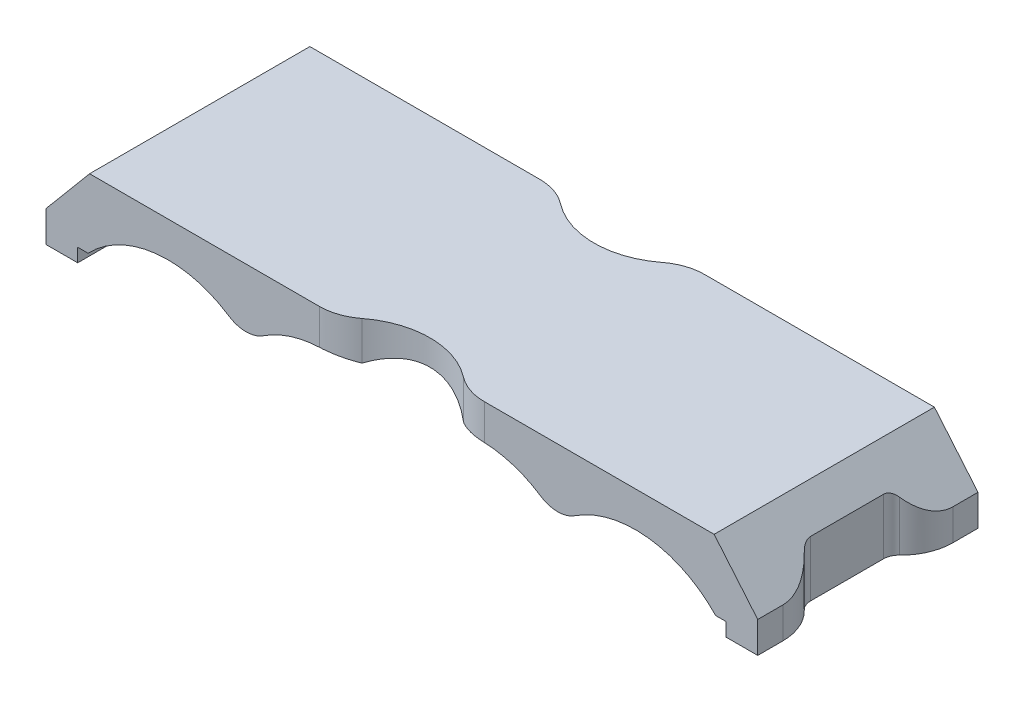
SolidWorks part; units mm, degrees
ref_plane "Front" through (0, 0, 0) normal (0, 0, 1) x (1, 0, 0)
ref_plane "Top" through (0, 0, 0) normal (0, 1, 0) x (1, 0, 0)
ref_plane "Right" through (0, 0, 0) normal (1, 0, 0) x (0, 0, -1)
ref_axis "Axis1" through (-84.4107, 0, 0) along (1, 0, 0)
ref_axis "Axis2" through (0, 64.3378, 0) along (0, -1, 0)
ref_axis "Axis3" through (0, 0, -102.329) along (0, 0, 1)
sketch "Sketch4" plane through (0, 0, 0) normal (0, 0, 1) x (1, 0, 0)
  line L0 (-34.25, 0) -> (34.25, 0)
  line L1 (34.25, 0) -> (34.25, -8)
  line L2 (31.2, -8) -> (31.2, -6.7)
  line L3 (31.2, -6.7) -> (30.2, -6.7)
  line L4 (31.2, -8) -> (34.25, -8)
  line L7 (0, -50) -> (0, 50) construction
  line L8 (-34.25, 0) -> (-34.25, -8)
  line L10 (-31.2, -8) -> (-34.25, -8)
  line L11 (-31.2, -6.7) -> (-30.2, -6.7)
  line L12 (-31.2, -8) -> (-31.2, -6.7)
  line L13 (-22.5, -3.4) -> (22.5, -3.4) construction
  arc A4 (-30.2, -6.7) -> (-15, -6.4956) centre (-22.5, -14.0333) cw
  arc A5 (-15, -6.4956) -> (0, -6.4956) centre (-7.5, -14.0333) cw
  arc A6 (0, -6.4956) -> (15, -6.4956) centre (7.5, -14.0333) cw
  arc A7 (15, -6.4956) -> (30.2, -6.7) centre (22.5, -14.0333) cw
  point P17 (-7.5, -3.4)
  point P20 (7.5, -3.4)
  dimension "D1" = 1
  dimension "D6" = 15
  dimension "D5" = 15
  dimension "D2" = 8
  dimension "D3" = 1.3
  dimension "D4" = 68.5
  dimension "D7" = 31.2
  dimension "D8" = 15
  dimension "D9" = 3.4
extrude "Boss-Extrude2" add sketch "Sketch4" along normal blind 21.2
chamfer "Chamfer1" distance 5 angle 40 2 edges at (34.25, 0, 10.6) (-34.25, 0, 10.6) first distance on face at (34.25, -4, 10.6) first distance on face at (-34.25, -4, 10.6)
sketch "Sketch5" plane through (0, 0, 0) normal (0, 1, 0) x (1, 0, 0)
  line L0 (30.0545, 0) -> (-30.0545, 0) construction
  line L1 (30.0545, -21.2) -> (-30.0545, -21.2) construction
  line L2 (-6, 0) -> (6, 0)
  line L3 (-6, -21.2) -> (6, -21.2)
  arc A0 (-6, 0) -> (6, 0) centre (0, 5.2915) ccw
  arc A1 (-6, -21.2) -> (6, -21.2) centre (0, -26.4915) cw
  point P8 (0, -2.7085)
  point P12 (0, -18.4915)
  dimension "D1" = 8
  dimension "D2" = 12
extrude "Cut-Extrude1" cut sketch "Sketch5" against normal through all
fillet "Fillet2" radius 5 4 edges at (6, -1.7532, 21.2) (-6, -1.7532, 21.2) (6, -1.7532, 0) (-6, -1.7532, 0)
fillet "Fillet3" radius 3 3 edges at (-15, -6.4956, 10.6) (0, -6.4956, 10.6) (15, -6.4956, 10.6)
sketch "Sketch6" plane through (0, 0, 0) normal (0, 1, 0) x (1, 0, 0)
  line L0 (34.25, 0) -> (34.25, -21.2) construction
  line L1 (34.25, -5.6) -> (33.75, -5.6)
  line L2 (34.25, -5.6) -> (34.25, -15.6)
  line L3 (34.25, -15.6) -> (33.75, -15.6)
  line L4 (32.25, -7.1) -> (32.25, -14.1)
  line L10 (0, -50) -> (0, 50) construction
  line L11 (-32.25, -7.1) -> (-32.25, -14.1)
  line L12 (-34.25, -15.6) -> (-33.75, -15.6)
  line L13 (-34.25, -5.6) -> (-34.25, -15.6)
  line L14 (-34.25, -5.6) -> (-33.75, -5.6)
  arc A0 (33.75, -15.6) -> (32.25, -14.1) centre (33.75, -14.1) cw
  arc A1 (33.75, -5.6) -> (32.25, -7.1) centre (33.75, -7.1) ccw
  arc A4 (-33.75, -5.6) -> (-32.25, -7.1) centre (-33.75, -7.1) cw
  arc A5 (-33.75, -15.6) -> (-32.25, -14.1) centre (-33.75, -14.1) ccw
  point P6 (34.25, -10.6)
  point P7 (34.25, -10.6)
  point P16 (32.25, -15.6)
  point P19 (32.25, -5.6)
  point P24 (-32.25, -5.6)
  point P25 (-32.25, -15.6)
  dimension "D3" = 1.5
  dimension "D1" = 10
  dimension "D2" = 2
extrude "Cut-Extrude2" cut sketch "Sketch6" against normal through all
fillet "Fillet4" radius 5 4 edges at (-34.25, -6.5, 15.6) (-34.25, -6.5, 5.6) (34.25, -6.5, 15.6) (34.25, -6.5, 5.6)
sketch "Sketch7" plane through (0, 0, 0) normal (0, 0, 1) x (1, 0, 0)
  arc A0 (-4.8878, -3.7259) -> (4.8878, -3.7259) centre (0, -12.45) cw
  arc A1 (4.8878, -3.7259) -> (1.6504, -5.1536) centre (7.5, -14.0333) ccw construction
  arc A2 (-1.6504, -5.1536) -> (1.6504, -5.1536) centre (0, -2.6484) ccw construction
  arc A3 (-1.6504, -5.1536) -> (-4.8878, -3.7259) centre (-7.5, -14.0333) ccw construction
  arc A4 (4.8878, -3.7259) -> (1.6504, -5.1536) centre (7.5, -14.0333) ccw
  arc A5 (-1.6504, -5.1536) -> (1.6504, -5.1536) centre (0, -2.6484) ccw
  arc A6 (-1.6504, -5.1536) -> (-4.8878, -3.7259) centre (-7.5, -14.0333) ccw
  dimension "D1" = 10
extrude "Cut-Extrude3" cut sketch "Sketch7" along normal through all
